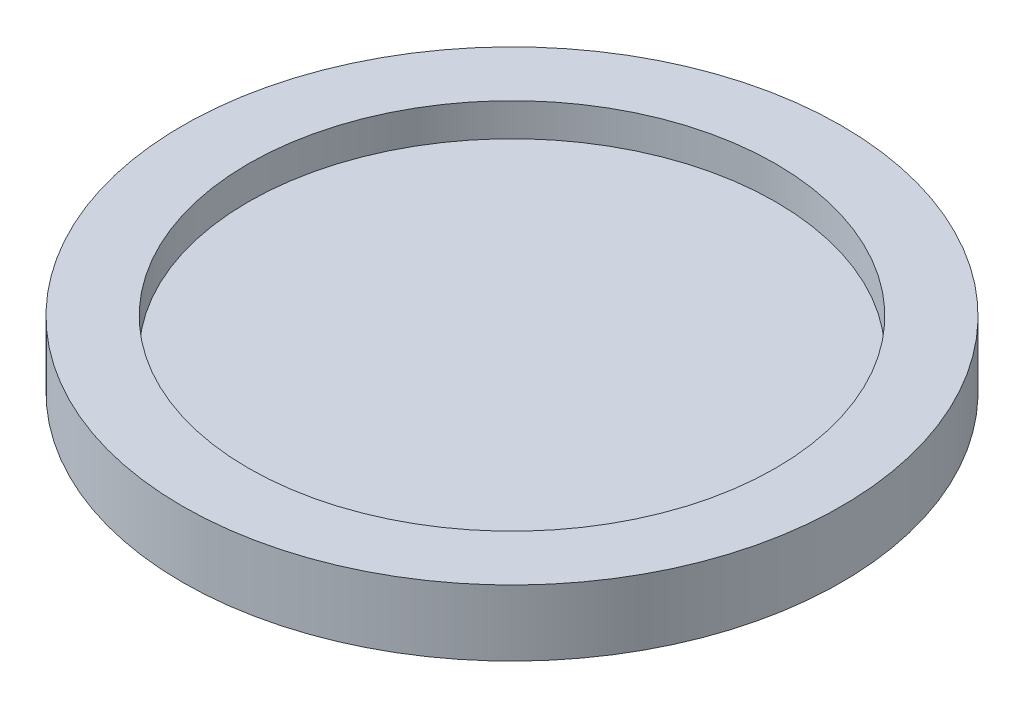
SolidWorks part; units mm, degrees
ref_plane "Front Plane" through (0, 0, 0) normal (0, 0, 1) x (1, 0, 0)
ref_plane "Top Plane" through (0, 0, 0) normal (0, 1, 0) x (1, 0, 0)
ref_plane "Right Plane" through (0, 0, 0) normal (1, 0, 0) x (0, 0, -1)
sketch "Sketch1" plane through (0, 0, 0) normal (0, 1, 0) x (1, 0, 0)
  circle A0 centre (0, 0) radius 5
  circle A1 centre (0, 0) radius 4
  dimension "D1" = 10
  dimension "D2" = 1
extrude "Boss-Extrude1" add sketch "Sketch1" along normal blind 1
extrude "Boss-Extrude2" add sketch "Sketch1<2>" along normal blind 0.5 contours A1 region at (0, 0, 0)
sketch "Sketch1<2>" plane through (0, 0, 0) normal (0, 1, 0) x (1, 0, 0) same geometry as "Sketch1"
